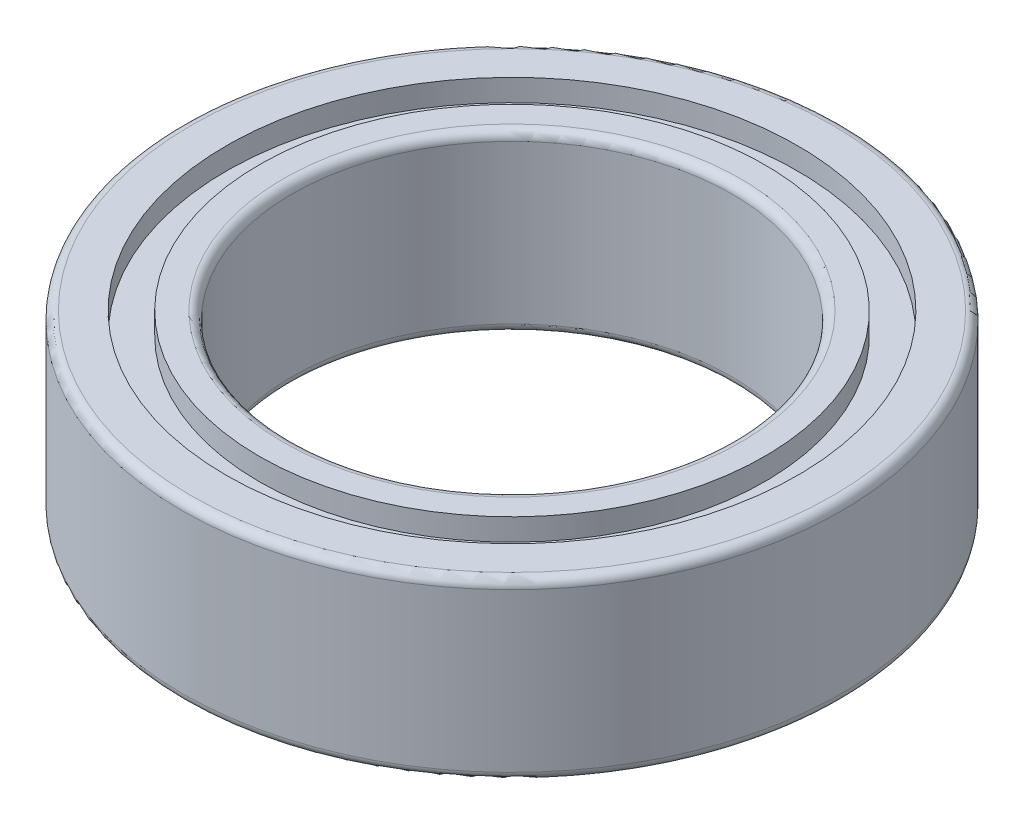
SolidWorks part; units mm, degrees
ref_plane "Front Plane" through (0, 0, 0) normal (0, 0, 1) x (1, 0, 0)
ref_plane "Top Plane" through (0, 0, 0) normal (0, 1, 0) x (1, 0, 0)
ref_plane "Right Plane" through (0, 0, 0) normal (1, 0, 0) x (0, 0, -1)
sketch "Sketch1" plane through (0, 0, 0) normal (0, 1, 0) x (1, 0, 0)
  circle A0 centre (0, 0) radius 7.5
  circle A1 centre (0, 0) radius 5
  dimension "D1" = 10
  dimension "D2" = 15
extrude "Boss-Extrude1" add sketch "Sketch1" along normal blind 2 and the other way blind 2
sketch "Sketch2" plane through (0, 2, 0) normal (0, 1, 0) x (1, 0, 0)
  circle A0 centre (0, 0) radius 5.75
  circle A1 centre (0, 0) radius 6.5
  dimension "D1" = 11.5
  dimension "D2" = 13
extrude "Cut-Extrude1" cut sketch "Sketch2" against normal blind 0.5
mirror "Mirror2" about plane through (0, 0, 0) normal (0, 1, 0) of "Cut-Extrude1"
fillet "Fillet1" radius 0.2 4 edges at (0, -2, 5) (0, 2, 5) (0, 2, 7.5) (0, -2, 7.5)
